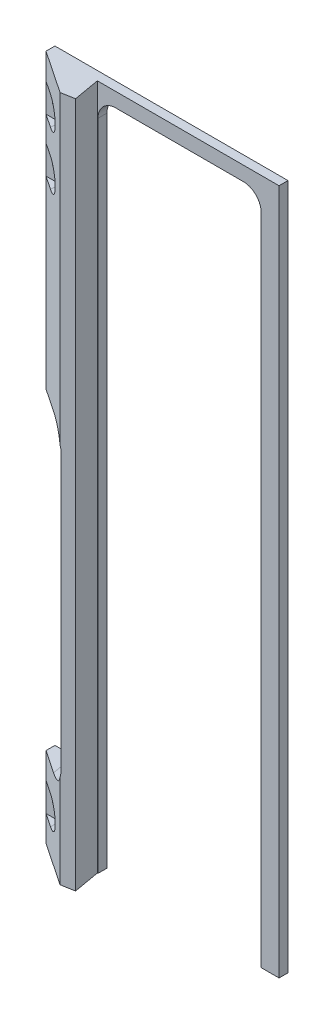
SolidWorks part; units mm, degrees
material "PET"
ref_plane "Front Plane" through (0, 0, 0) normal (0, 0, 1) x (1, 0, 0)
ref_plane "Top Plane" through (0, 0, 0) normal (0, 1, 0) x (1, 0, 0)
ref_plane "Right Plane" through (0, 0, 0) normal (1, 0, 0) x (0, 0, -1)
sketch "Sketch2" plane through (0, 0, 0) normal (0, 0, 1) x (1, 0, 0)
  line L1 (828.7686, 5932.0525) -> (911.5067, 5932.0525)
  line L2 (828.7686, 5932.0525) -> (828.7686, 6175.6509)
  line L3 (828.7686, 6175.6509) -> (911.5067, 6175.6509)
  line L4 (911.5067, 5932.0525) -> (911.5067, 6175.6509)
extrude "Boss-Extrude1" add sketch "Sketch2" along normal blind 3.175
sketch "Sketch5" plane through (0, 6175.6509, 0) normal (0, 1, 0) x (1, 0, 0)
  line L0 (828.7686, -3.175) -> (843.957, -13.3823)
  line L1 (843.957, -13.3823) -> (848.6471, -12.5553)
  line L2 (848.6471, -12.5553) -> (846.9931, -3.175)
  line L3 (822.1814, 34.0849) -> (828.1915, 0) construction
  line L4 (846.9931, -3.175) -> (828.7686, -3.175)
  dimension "D1" = 9.525
  dimension "D2" = 18.2245
  dimension "D3" = 4.7625
extrude "Boss-Extrude2" add sketch "Sketch5" against normal through all
sketch "Sketch3" plane through (1789.9898, 0, -153.4288) normal (-0.1736, 0, -0.9848) x (-0.9848, 0, 0.1736)
  line L0 (973.812, 6175.6509) -> (973.812, 5932.0525) construction
  line L1 (973.812, 6071.7525) -> (960.35, 6071.7525)
  line L2 (973.812, 6071.7525) -> (973.812, 5960.6275)
  line L3 (973.812, 5960.6275) -> (960.35, 5960.6275)
  line L4 (960.35, 6071.7525) -> (960.35, 5960.6275)
  line L6 (955.8644, 5932.0525) -> (892.3309, 5932.0525) construction
  dimension "D1" = 13.462
  dimension "D2" = 28.575
  dimension "D3" = 111.125
extrude "Cut-Extrude1" cut sketch "Sketch3" against normal through all both and the other way through all
fillet "Fillet1" radius 6.35 2 edges at (843.0541, 6071.7525, 6.6671) (843.0541, 5960.6275, 6.6671)
sketch "Sketch4" plane through (0, 0, 3.175) normal (0, 0, 1) x (1, 0, 0)
  line L0 (905.1567, 6170.5709) -> (847.2008, 6170.5709)
  line L4 (911.5067, 6175.6509) -> (846.9931, 6175.6509) construction
  line L8 (911.5067, 5932.0525) -> (911.5067, 6175.6509) construction
  line L9 (847.2008, 6170.5709) -> (847.2008, 5932.0525)
  line L10 (847.2008, 5932.0525) -> (905.1567, 5932.0525)
  line L11 (905.1567, 5932.0525) -> (905.1567, 6170.5709)
  line L12 (842.4383, 5966.9775) -> (842.4383, 6065.4025) construction
  line L13 (846.9931, 5932.0525) -> (911.5067, 5932.0525) construction
  dimension "D1" = 5.08
  dimension "D2" = 4.7625
  dimension "D3" = 6.35
  dimension "D4" = 0
extrude "Cut-Extrude2" cut sketch "Sketch4" against normal through all
fillet "Fillet2" radius 6.35 2 edges at (847.2008, 6170.5709, 1.5875) (905.1567, 6170.5709, 1.5875)
hole_wizard "#6 (0.204) Diameter Hole1" positions "Sketch6" profile "Sketch7" hole size "#6" standard "ANSI Inch" end condition through all
sketch "Sketch6" plane through (0, 0, 0) normal (0, 0, -1) x (-1, 0, 0)
  line L0 (-911.5067, 6175.6509) -> (-828.7686, 6175.6509) construction
  line L1 (-828.7686, 5932.0525) -> (-847.2008, 5932.0525) construction
  line L2 (-828.7686, 6175.6509) -> (-828.7686, 6071.7525) construction
  point P0 (-833.6581, 6161.3634)
  point P2 (-833.6581, 6142.3134)
  point P4 (-833.6581, 5946.34)
  dimension "D1" = 14.2875
  dimension "D2" = 14.2875
  dimension "D3" = 4.8895
  dimension "D4" = 19.05
sketch "Sketch7" plane through (833.6581, 6161.3634, 0) normal (1, 0, 0) x (0, 1, 0)
  line L0 (0, 0) -> (0, 13.3823)
  line L1 (0, 13.3823) -> (2.5908, 13.3823)
  line L2 (2.5908, 13.3823) -> (2.5908, 0)
  line L5 (2.5908, 0) -> (0, 0)
  line L11 (0, -6.35) -> (0, 107.95) construction
  dimension "Thru Hole Dia." = 5.1816
  dimension "Thru Hole Depth" = 13.3823
sketch "Sketch8" plane through (0, 0, 3.175) normal (0, 0, 1) x (1, 0, 0)
  line L2 (833.6581, 6161.3634) -> (828.7686, 6161.3634) construction
  line L3 (833.6581, 6156.2834) -> (828.7686, 6156.2834)
  line L4 (833.6581, 6166.4434) -> (828.7686, 6166.4434)
  line L5 (828.7686, 6175.6509) -> (828.7686, 6071.7525) construction
  line L6 (833.6581, 6142.3134) -> (828.7686, 6142.3134) construction
  line L7 (833.6581, 6137.2334) -> (828.7686, 6137.2334)
  line L8 (833.6581, 6147.3934) -> (828.7686, 6147.3934)
  line L9 (833.6581, 5946.34) -> (828.7686, 5946.34) construction
  line L10 (828.7686, 5960.6275) -> (828.7686, 5932.0525) construction
  line L11 (833.6581, 5941.26) -> (828.7686, 5941.26)
  line L12 (833.6581, 5951.42) -> (828.7686, 5951.42)
  arc A3 (833.6581, 6156.2834) -> (833.6581, 6166.4434) centre (833.6581, 6161.3634) ccw
  arc A4 (828.7686, 6166.4434) -> (828.7686, 6156.2834) centre (828.7686, 6161.3634) ccw
  arc A5 (833.6581, 6137.2334) -> (833.6581, 6147.3934) centre (833.6581, 6142.3134) ccw
  arc A6 (828.7686, 6147.3934) -> (828.7686, 6137.2334) centre (828.7686, 6142.3134) ccw
  arc A7 (833.6581, 5941.26) -> (833.6581, 5951.42) centre (833.6581, 5946.34) ccw
  arc A8 (828.7686, 5951.42) -> (828.7686, 5941.26) centre (828.7686, 5946.34) ccw
  point P3 (831.2134, 6161.3634)
  point P10 (831.2134, 6142.3134)
  point P21 (831.2134, 5946.34)
  dimension "D1" = 5.08
extrude "Cut-Extrude3" cut sketch "Sketch8" along normal through all
